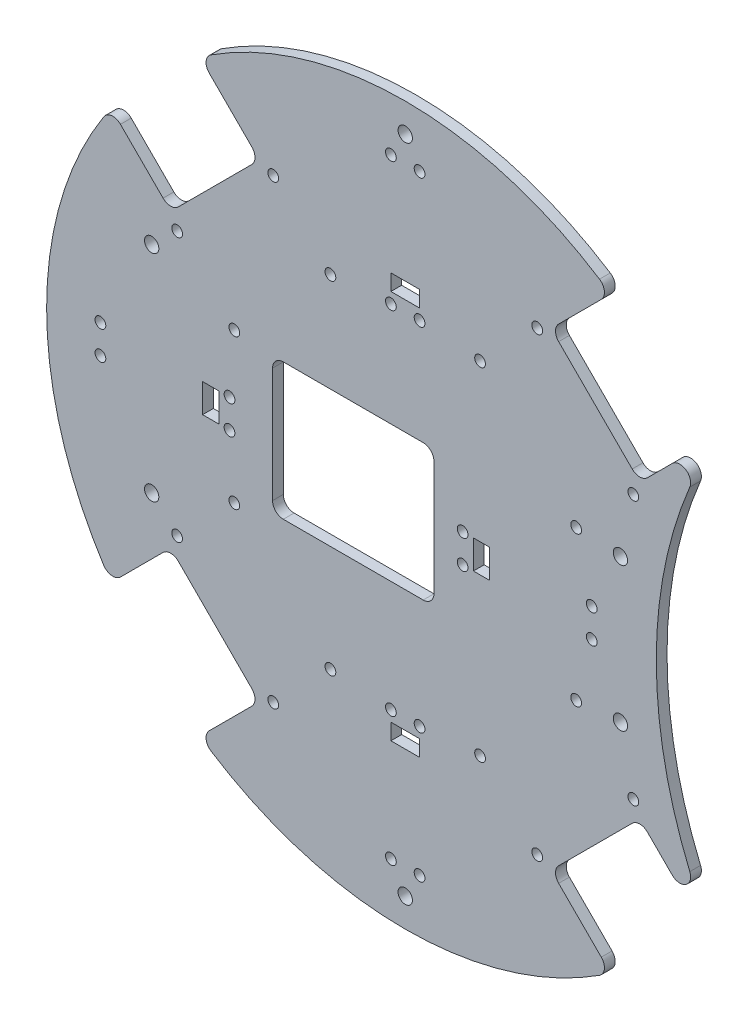
SolidWorks part; units mm, degrees
ref_plane "Alzado" through (0, 0, 0) normal (0, 0, 1) x (1, 0, 0)
ref_plane "Planta" through (0, 0, 0) normal (0, 1, 0) x (1, 0, 0)
ref_plane "Vista lateral" through (0, 0, 0) normal (1, 0, 0) x (0, 0, -1)
sketch "Croquis1" plane through (0, 0, 0) normal (0, 0, 1) x (1, 0, 0)
  circle A0 centre (0, 0) radius 100
  dimension "D1" = 200
extrude "Saliente-Extruir1" add sketch "Croquis1" along normal blind 3
sketch "Croquis3" plane through (0, 0, 3) normal (0, 0, 1) x (1, 0, 0)
  line L0 (0, 0) -> (190, 0) construction
  circle A0 centre (190, 0) radius 120
  dimension "D1" = 240
  dimension "D2" = 190
extrude "Cortar-Extruir1" cut sketch "Croquis3" against normal blind 3
sketch "Croquis5" plane through (0, 0, 3) normal (0, 0, 1) x (1, 0, 0)
  line L0 (0, -100) -> (0, 100) construction
  line L1 (-100, 0) -> (70, 0) construction
  line L2 (0, 0) -> (-70.7107, -70.7107) construction
  line L3 (-70.7107, -70.7107) -> (70.7107, 70.7107) construction
  line L4 (0, 0) -> (-70.7107, 70.7107) construction
  line L5 (-70.7107, 70.7107) -> (70.7107, -70.7107) construction
  line L6 (-70.7107, -70.7107) -> (-58.3363, -83.085) construction
  line L9 (-58.3363, -83.085) -> (-83.085, -58.3363)
  line L11 (-83.085, -58.3363) -> (-65.4074, -40.6586)
  line L12 (-65.4074, -40.6586) -> (-40.6586, -65.4074)
  line L13 (-40.6586, -65.4074) -> (-58.3363, -83.085)
  line L14 (-70.7107, 70.7107) -> (-83.085, 58.3363) construction
  line L15 (-83.085, 58.3363) -> (-100, 0) construction
  line L17 (-83.085, 58.3363) -> (-58.3363, 83.085)
  line L18 (-58.3363, 83.085) -> (-40.6586, 65.4074)
  line L19 (-40.6586, 65.4074) -> (-65.4074, 40.6586)
  line L20 (-65.4074, 40.6586) -> (-83.085, 58.3363)
  line L22 (70.7107, -70.7107) -> (58.3363, -83.085) construction
  line L23 (58.3363, -83.085) -> (0, -100) construction
  line L24 (58.3363, -83.085) -> (83.085, -58.3363)
  line L25 (83.085, -58.3363) -> (65.4074, -40.6586)
  line L26 (65.4074, -40.6586) -> (40.6586, -65.4074)
  line L27 (40.6586, -65.4074) -> (58.3363, -83.085)
  line L28 (70.7107, 70.7107) -> (58.3363, 83.085) construction
  line L29 (58.3363, 83.085) -> (0, 100) construction
  line L30 (58.3363, 83.085) -> (83.085, 58.3363)
  line L31 (83.085, 58.3363) -> (65.4074, 40.6586)
  line L32 (65.4074, 40.6586) -> (40.6586, 65.4074)
  line L33 (40.6586, 65.4074) -> (58.3363, 83.085)
  arc A0 (83.4211, 55.1446) -> (83.4211, -55.1446) centre (0, 0) ccw construction
  arc A1 (83.4211, 55.1446) -> (83.4211, -55.1446) centre (190, 0) ccw construction
  point P36 (0, 0)
  dimension "D2" = 17.5
  dimension "D3" = 25
  dimension "D4" = 35
  dimension "D5" = 25
  dimension "D6" = 35
  dimension "D8" = 25
  dimension "D9" = 17.5
  dimension "D7" = 35
  dimension "D10" = 90
  dimension "D11" = 17.5
  dimension "D12" = 17.5
  dimension "D13" = 35
  dimension "D14" = 25
  dimension "D15" = 134.3503
  dimension "D16" = 100
extrude "Cortar-Extruir6" cut sketch "Croquis5" against normal blind 10
sketch "Croquis12" plane through (0, 0, 3) normal (0, 0, 1) x (1, 0, 0)
  line L0 (-53.033, -53.033) -> (-39.9421, -50.0116) construction
  line L1 (-40.6586, -65.4074) -> (-65.4074, -40.6586) construction
  line L2 (-39.9421, -50.0116) -> (-36.8049, -63.6043) construction
  line L3 (-36.8049, -63.6043) -> (-63.6043, -36.8049) construction
  line L4 (-63.6043, -36.8049) -> (-47.6661, -20.8667) construction
  line L6 (53.033, -53.033) -> (-53.033, 53.033) construction
  line L7 (65.4074, -40.6586) -> (40.6586, -65.4074) construction
  line L8 (-65.4074, 40.6586) -> (-40.6586, 65.4074) construction
  line L9 (36.8049, 63.6043) -> (20.8667, 47.6661) construction
  line L10 (63.6043, 36.8049) -> (36.8049, 63.6043) construction
  line L11 (50.0116, 39.9421) -> (63.6043, 36.8049) construction
  line L12 (53.033, 53.033) -> (50.0116, 39.9421) construction
  line L14 (53.033, -53.033) -> (50.2046, -50.2046) construction
  line L15 (50.2046, -50.2046) -> (36.8049, -63.6043) construction
  line L16 (36.8049, -63.6043) -> (63.6043, -36.8049) construction
  line L17 (63.6043, -36.8049) -> (47.6661, -20.8667) construction
  line L19 (-53.033, -53.033) -> (53.033, 53.033) construction
  line L20 (-36.8049, 63.6043) -> (-20.8667, 47.6661) construction
  line L21 (-63.6043, 36.8049) -> (-36.8049, 63.6043) construction
  line L22 (-50.2046, 50.2046) -> (-63.6043, 36.8049) construction
  line L23 (-53.033, 53.033) -> (-50.2046, 50.2046) construction
  circle A0 centre (-63.6043, -36.8049) radius 1.5
  circle A1 centre (-36.8049, -63.6043) radius 1.5
  circle A2 centre (-47.6661, -20.8667) radius 1.5
  circle A3 centre (-20.8667, -47.6661) radius 1.5
  circle A5 centre (47.6661, 20.8667) radius 1.5
  circle A6 centre (20.8667, 47.6661) radius 1.5
  circle A7 centre (63.6043, 36.8049) radius 1.5
  circle A8 centre (36.8049, 63.6043) radius 1.5
  circle A10 centre (20.8667, -47.6661) radius 1.5
  circle A11 centre (47.6661, -20.8667) radius 1.5
  circle A12 centre (63.6043, -36.8049) radius 1.5
  circle A13 centre (36.8049, -63.6043) radius 1.5
  circle A15 centre (-63.6043, 36.8049) radius 1.5
  circle A16 centre (-36.8049, 63.6043) radius 1.5
  circle A17 centre (-20.8667, 47.6661) radius 1.5
  circle A18 centre (-47.6661, 20.8667) radius 1.5
  dimension "D2" = 3
  dimension "D3" = 3
  dimension "D4" = 4
  dimension "D5" = 4
  dimension "D6" = 3
  dimension "D7" = 3
  dimension "D8" = 37.9
  dimension "D9" = 22.54
  dimension "D10" = 22.54
  dimension "D11" = 37.9
  dimension "D12" = 18.95
  dimension "D13" = 18.95
  dimension "D14" = 3
  dimension "D15" = 3
  dimension "D16" = 3
  dimension "D17" = 3
  dimension "D18" = 37.9
  dimension "D19" = 22.54
  dimension "D20" = 22.54
  dimension "D21" = 37.9
  dimension "D22" = 4
  dimension "D1" = 13.95
extrude "Cortar-Extruir7" cut sketch "Croquis12" against normal through all
sketch "Croquis9" plane through (0, 0, 3) normal (0, 0, 1) x (1, 0, 0)
  line L0 (0, 0) -> (-100, 0) construction
  line L5 (0, 100) -> (0, -100) construction
  line L6 (19, 4) -> (23.5, 4)
  line L7 (19, 4) -> (19, -4)
  line L8 (19, -4) -> (23.5, -4)
  line L9 (23.5, 4) -> (23.5, -4)
  line L10 (-4, -52) -> (4, -52)
  line L11 (-52, 4) -> (-56.5, 4)
  line L12 (-52, 4) -> (-52, -4)
  line L13 (-52, -4) -> (-56.5, -4)
  line L14 (-56.5, 4) -> (-56.5, -4)
  line L15 (-4, 56.5) -> (4, 56.5)
  line L16 (-4, 56.5) -> (-4, 52)
  line L17 (-4, 52) -> (4, 52)
  line L18 (4, 56.5) -> (4, 52)
  line L19 (4, -56.5) -> (4, -52)
  line L20 (-4, -56.5) -> (4, -56.5)
  line L21 (-4, -56.5) -> (-4, -52)
  line L22 (0, 0) -> (70, 0) construction
  line L24 (-52.061, -4) -> (-52.0837, -4) construction
  circle A0 centre (52, -4) radius 1.5
  circle A1 centre (16, 4) radius 1.5
  circle A4 centre (52, 4) radius 1.5
  circle A5 centre (16, -4) radius 1.5
  arc A6 (-81.9939, 57.2451) -> (-81.9939, -57.2451) centre (0, 0) ccw construction
  arc A7 (83.4211, 55.1446) -> (83.4211, -55.1446) centre (190, 0) ccw construction
  circle A8 centre (-85, 4) radius 1.5
  circle A9 centre (-85, -4) radius 1.5
  circle A10 centre (-49, 4) radius 1.5
  circle A11 centre (-49, -4) radius 1.5
  circle A12 centre (-4, 85) radius 1.5
  circle A13 centre (4, 85) radius 1.5
  circle A14 centre (-4, 49) radius 1.5
  circle A15 centre (4, 49) radius 1.5
  circle A20 centre (-4, -49) radius 1.5
  circle A21 centre (4, -49) radius 1.5
  circle A22 centre (4, -85) radius 1.5
  circle A23 centre (-4, -85) radius 1.5
  arc A25 (57.2451, 81.9939) -> (-57.2451, 81.9939) centre (0, 0) ccw construction
  dimension "D6" = 16
  dimension "D7" = 3
  dimension "D8" = 36
  dimension "D9" = 36
  dimension "D10" = 3
  dimension "D11" = 3
  dimension "D12" = 4
  dimension "D13" = 4
  dimension "D14" = 3
  dimension "D15" = 3
  dimension "D16" = 3
  dimension "D21" = 4
  dimension "D22" = 4
  dimension "D23" = 3
  dimension "D24" = 3
  dimension "D25" = 4
  dimension "D26" = 4
  dimension "D27" = 36
  dimension "D28" = 36
  dimension "D29" = 85
  dimension "D30" = 85
  dimension "D35" = 3
  dimension "D36" = 3
  dimension "D37" = 8
  dimension "D38" = 4
  dimension "D39" = 3
  dimension "D40" = 3
  dimension "D41" = 8
  dimension "D42" = 36
  dimension "D43" = 36
  dimension "D44" = 36
  dimension "D45" = 4
  dimension "D46" = 4
  dimension "D51" = 4
  dimension "D52" = 4
  dimension "D53" = 16
  dimension "D55" = 36
  dimension "D56" = 49
  dimension "D57" = 49
  dimension "D58" = 3
  dimension "D59" = 3
  dimension "D60" = 3
  dimension "D61" = 3
  dimension "D62" = 4.5
  dimension "D32" = 8
  dimension "D64" = 0
  dimension "D69" = 8
  dimension "D70" = 4
  dimension "D71" = 85.0941
  dimension "D72" = 85.0941
  dimension "D17" = 4.5
  dimension "D18" = 8
  dimension "D19" = 3
  dimension "D20" = 0
  dimension "D31" = 3.061
  dimension "D33" = 3
  dimension "D34" = 0
  dimension "D47" = 8
  dimension "D48" = 4.5
  dimension "D49" = 0
  dimension "D50" = 3
  dimension "D54" = 4
  dimension "D63" = 0
  dimension "D65" = 3
  dimension "D66" = 4.5
  dimension "D67" = 8
  dimension "D68" = 3
extrude "Cortar-Extruir5" cut sketch "Croquis9" against normal blind 10
sketch "Croquis13" plane through (0, 0, 3) normal (0, 0, 1) x (1, 0, 0)
  line L0 (0, 100) -> (0, -100) construction
  line L1 (-100, 0) -> (70, 0) construction
  line L2 (-70.7107, 70.7107) -> (70.7107, -70.7107) construction
  line L3 (-70.7093, -70.7093) -> (70.712, 70.712) construction
  line L4 (-70.7107, 70.7107) -> (-70.7093, -70.7093) construction
  line L5 (-70.7093, -70.7093) -> (70.7107, -70.7107) construction
  line L6 (70.7107, -70.7107) -> (70.712, 70.712) construction
  line L7 (70.712, 70.712) -> (-70.7107, 70.7107) construction
  line L9 (-37, 20) -> (8, 20)
  line L10 (-37, 20) -> (-37, -18)
  line L11 (-37, -18) -> (8, -18)
  line L12 (8, 20) -> (8, -18)
  arc A0 (57.2451, 81.9939) -> (-57.2451, 81.9939) centre (0, 0) ccw construction
  arc A1 (-57.2451, -81.9939) -> (57.2451, -81.9939) centre (0, 0) ccw construction
  arc A2 (-81.9939, 57.2451) -> (-81.9939, -57.2451) centre (0, 0) ccw construction
  arc A3 (83.4211, 55.1446) -> (83.4211, -55.1446) centre (190, 0) ccw construction
  circle A4 centre (-70.7103, 30) radius 2
  circle A5 centre (-70.7097, -30) radius 2
  circle A8 centre (0, -92) radius 2
  circle A9 centre (0, 92) radius 2
  circle A10 centre (60, -20) radius 2
  circle A11 centre (60, 20) radius 2
  point P37 (-15, 0)
  dimension "D9" = 4
  dimension "D10" = 4
  dimension "D11" = 30
  dimension "D12" = 30
  dimension "D13" = 4
  dimension "D14" = 4
  dimension "D15" = 60
  dimension "D16" = 60
  dimension "D17" = 4
  dimension "D18" = 92
  dimension "D19" = 92
  dimension "D20" = 4
  dimension "D25" = 20
  dimension "D26" = 20
  dimension "D1" = 45
  dimension "D2" = 200
  dimension "D3" = 0
  dimension "D4" = 200
  dimension "D5" = 45
  dimension "D6" = 0
  dimension "D7" = 141.42
  dimension "D8" = 141.42
  dimension "D21" = 45
  dimension "D22" = 38
  dimension "D23" = 18
  dimension "D24" = 37
extrude "Cortar-Extruir8" cut sketch "Croquis13" against normal through all
fillet "Redondeo2" radius 3 20 edges at (-81.9939, 57.2451, 1.5) (-65.4074, 40.6586, 1.5) (-40.6586, 65.4074, 1.5) (-57.2451, 81.9939, 1.5) (65.4074, 40.6586, 1.5) (40.6586, 65.4074, 1.5) (57.2451, 81.9939, 1.5) (81.9939, 57.2451, 1.5) (65.4074, -40.6586, 1.5) (40.6586, -65.4074, 1.5) (81.9939, -57.2451, 1.5) (57.2451, -81.9939, 1.5) (-65.4074, -40.6586, 1.5) (-81.9939, -57.2451, 1.5) (-57.2451, -81.9939, 1.5) (-40.6586, -65.4074, 1.5) (8, -18, 1.5) (8, 20, 1.5) (-37, -18, 1.5) (-37, 20, 1.5)
fillet "Redondeo3" radius 3 2 edges at (83.4211, -55.1446, 1.5) (83.4211, 55.1446, 1.5)
